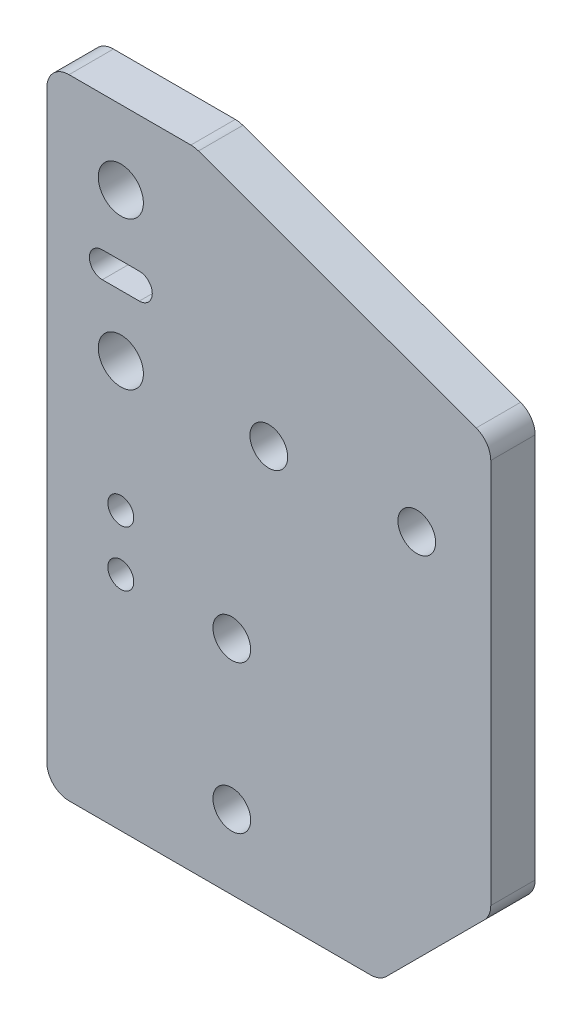
SolidWorks part; units mm, degrees
material "Acrylic (Medium-high impact)"
ref_plane "Спереди" through (0, 0, 0) normal (0, 0, 1) x (1, 0, 0)
ref_plane "Сверху" through (0, 0, 0) normal (0, 1, 0) x (1, 0, 0)
ref_plane "Справа" through (0, 0, 0) normal (1, 0, 0) x (0, 0, -1)
sketch "Model" plane through (0, 0, 0) normal (0, 0, 1) x (1, 0, 0)
  line L0 (59.1213, 14.1213) -> (45.8787, 0.8787)
  line L2 (5.4335, 55) -> (15.2657, 55) construction
  line L3 (5.6697, 75) -> (14.2485, 75) construction
  line L4 (10, 75) -> (10, 55) construction
  line L5 (12.5, 65) -> (7.5, 65) construction
  line L6 (12.5, 63.25) -> (7.5, 63.25)
  line L7 (12.5, 66.75) -> (7.5, 66.75)
  line L12 (3, 0) -> (43.7574, 0)
  line L13 (60, 16.2426) -> (60, 68.3406)
  line L14 (58.0261, 71.1596) -> (20.4971, 84.8191)
  line L8721 (3, 85) -> (19.471, 85)
  line L8759 (0, 3) -> (0, 82)
  arc A0 (58.0261, 71.1596) -> (60, 68.3406) centre (57, 68.3406) cw
  arc A1 (20.4971, 84.8191) -> (19.471, 85) centre (19.471, 82) ccw
  arc A2 (60, 16.2426) -> (59.1213, 14.1213) centre (57, 16.2426) cw
  circle A3 centre (10, 75) radius 3.05
  circle A4 centre (10, 55) radius 3.05
  arc A5 (0, 82) -> (3, 85) centre (3, 82) cw
  arc A6 (0, 3) -> (3, 0) centre (3, 3) ccw
  arc A7 (45.8787, 0.8787) -> (43.7574, 0) centre (43.7574, 3) cw
  arc A8 (12.5, 63.25) -> (12.5, 66.75) centre (12.5, 65) ccw
  arc A9 (7.5, 66.75) -> (7.5, 63.25) centre (7.5, 65) ccw
  circle A11 centre (30, 55) radius 2.55
  circle A12 centre (50, 55) radius 2.55
  point P17 (20, 85)
  point P30 (0, 85)
  point P32 (45, 0)
  point P33 (0, 0)
  point P35 (20, 85)
  point P37 (10, 65)
  dimension "D16" = 6.1
  dimension "D18" = 45
  dimension "D19" = 3
  dimension "D28" = 5.1
  dimension "D6" = 60
  dimension "D13" = 5
  dimension "D4" = 85
  dimension "D5" = 10
  dimension "D7" = 20
  dimension "D8" = 10
  dimension "D9" = 70
  dimension "D10" = 10
  dimension "D11" = 3.5
  dimension "D12" = 20
  dimension "D15" = 45
  dimension "D30" = 20
  dimension "D31" = 20
extrude "Body" add sketch "Model" along normal blind 6
sketch "Sketch1" plane through (0, 0, 0) normal (0, 0, -1) x (-1, 0, 0)
  line L0 (-10, 43.645) -> (-10, 21.6609) construction
  line L3 (0, 82) -> (0, 3) construction
  line L4 (-3, 0) -> (-43.7574, 0) construction
  circle A0 centre (-10, 30) radius 1.75
  circle A1 centre (-10, 37.5) radius 1.75
  dimension "D1" = 3.5
  dimension "D3" = 7.5
  dimension "D4" = 30
  dimension "D5" = 10
extrude "ForSensor" cut sketch "Sketch1" against normal blind 10 contours A0 | A1
sketch "Sketch2" [suppressed] plane through (0, 0, 6) normal (0, 0, 1) x (1, 0, 0)
  line L0 (60, 16.2426) -> (60, 68.3406) construction
  line L1 (3, 0) -> (43.7574, 0) construction
  circle A0 centre (44, 26) radius 11
  dimension "D1" = 22
  dimension "D2" = 16
  dimension "D3" = 26
extrude "CableIHoleInput" [suppressed] cut sketch "Sketch2" against normal through all
sketch "Sketch3" [suppressed] plane through (0, 0, 6) normal (0, 0, 1) x (1, 0, 0)
  line L0 (0, 82) -> (0, 3) construction
  line L1 (3, 0) -> (43.7574, 0) construction
  circle A0 centre (6.5, 29) radius 1.75
  circle A1 centre (6.5, 20) radius 1.75
  dimension "D2" = 3.5
  dimension "D1" = 6.5
  dimension "D3" = 9
  dimension "D4" = 20
extrude "CableMount" [suppressed] cut sketch "Sketch3" against normal through all
hole_wizard "Ø5.1 (5.1) FootingMount" positions "Sketch5" profile "Sketch6" hole size "Ø5.1" standard "ANSI Metric" end condition through all
sketch "Sketch5" plane through (0, 0, 6) normal (0, 0, 1) x (1, 0, 0)
  line L0 (3, 0) -> (43.7574, 0) construction
  line L1 (0, 82) -> (0, 3) construction
  point P0 (25, 10)
  point P2 (25, 30)
  dimension "D1" = 10
  dimension "D2" = 30
  dimension "D3" = 25
sketch "Sketch6" plane through (25, 10, 6) normal (1, 0, 0) x (0, -1, 0)
  line L0 (0, 0) -> (0, 6)
  line L1 (0, 6) -> (2.55, 6)
  line L2 (2.55, 6) -> (2.55, 0)
  line L5 (2.55, 0) -> (0, 0)
  line L11 (0, -6.35) -> (0, 107.95) construction
  dimension "Thru Hole Dia." = 5.1
  dimension "Thru Hole Depth" = 6
